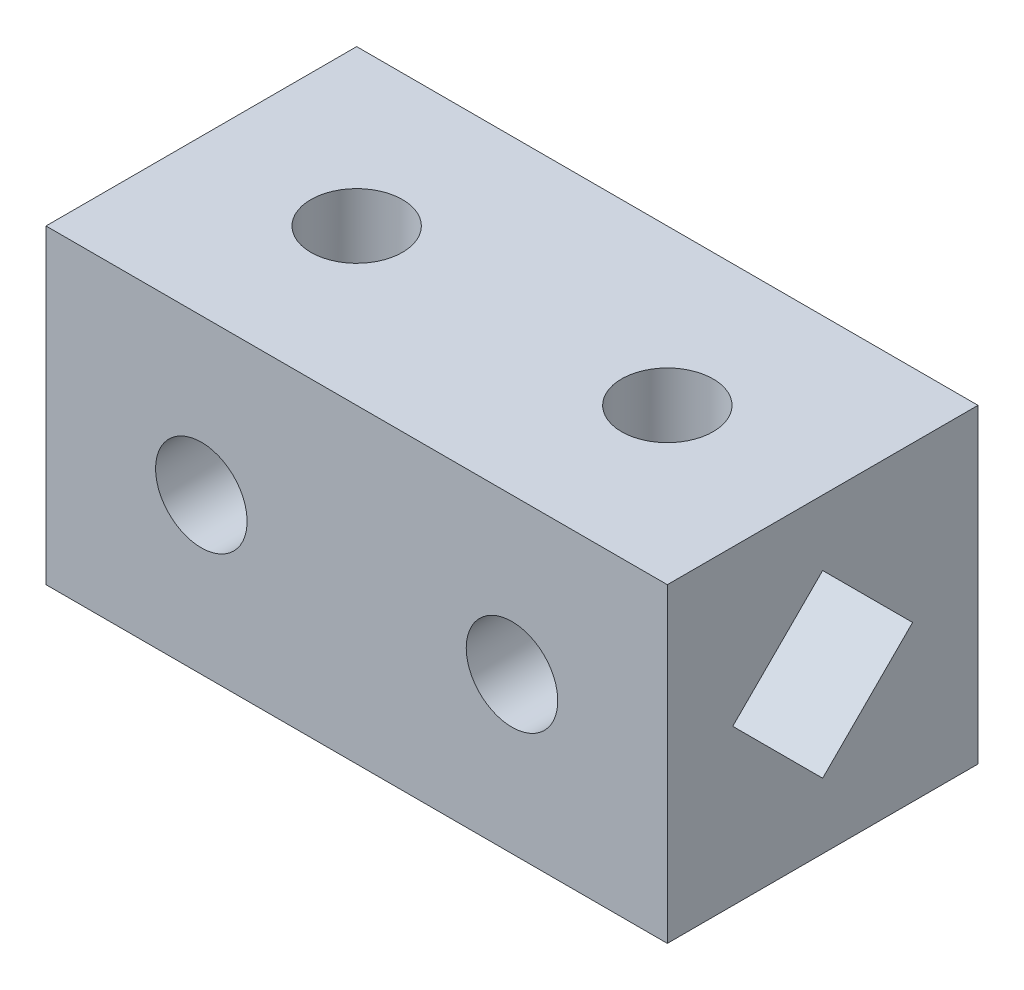
SolidWorks part; units mm, degrees
ref_plane "Front Plane" through (0, 0, 0) normal (0, 0, 1) x (1, 0, 0)
ref_plane "Top Plane" through (0, 0, 0) normal (0, 1, 0) x (1, 0, 0)
ref_plane "Right Plane" through (0, 0, 0) normal (1, 0, 0) x (0, 0, -1)
other "Configuration Table"
sketch "sketch1" plane through (0, 0, 0) normal (0, 1, 0) x (1, 0, 0)
  line L0 (0, -8.5) -> (8.5, -8.5) construction
  line L1 (0, 0) -> (34, 0)
  line L2 (0, 0) -> (0, -17)
  line L3 (0, -17) -> (34, -17)
  line L4 (34, 0) -> (34, -17)
  line L5 (8.5, -8.5) -> (25.5, -8.5) construction
  circle A1 centre (8.5, -8.5) radius 2.505
  circle A2 centre (25.5, -8.5) radius 2.505
  dimension "D4" = 5.01
  dimension "D1" = 17
  dimension "D2" = 34
  dimension "D3" = 8.5
  dimension "D6" = 17
extrude "Boss-Extrude1" add sketch "sketch1" along normal blind 17
sketch "Sketch6" plane through (0, 0, 0) normal (0, 0, -1) x (-1, 0, 0)
  line L0 (-34, 8.5) -> (-25.5, 8.5) construction
  line L1 (-25.5, 8.5) -> (-8.5, 8.5) construction
  line L4 (-34, 0) -> (0, 0)
  line L5 (0, 0) -> (0, 17)
  line L6 (0, 17) -> (-34, 17)
  line L7 (-34, 17) -> (-34, 0)
  line L8 (-34, 0) -> (0, 0)
  line L9 (0, 0) -> (0, 17)
  line L10 (0, 17) -> (-34, 17)
  line L11 (-34, 17) -> (-34, 0)
  circle A0 centre (-25.5, 8.5) radius 2.505
  circle A1 centre (-8.5, 8.5) radius 2.505
  dimension "D3" = 5.01
  dimension "D2" = 8.5
  dimension "D5" = 17
  dimension "D4" = 2
extrude "Cut-Extrude10" cut sketch "Sketch6" against normal through all flip side to cut
sketch "Sketch7" plane through (34, 0, 0) normal (1, 0, 0) x (0, 0, -1)
  line L0 (-17, 8.5) -> (0, 8.5) construction
  line L1 (-8.5, 8.5) -> (-8.5, 13.4215) construction
  line L2 (-8.5, 13.4215) -> (-3.5785, 8.5)
  line L3 (-3.5785, 8.5) -> (-8.5, 3.5785)
  line L4 (-17, 0) -> (0, 0)
  line L5 (0, 0) -> (0, 17)
  line L6 (0, 17) -> (-17, 17)
  line L7 (-17, 17) -> (-17, 0)
  line L8 (-17, 0) -> (0, 0)
  line L9 (0, 0) -> (0, 17)
  line L10 (0, 17) -> (-17, 17)
  line L11 (-17, 17) -> (-17, 0)
  line L12 (-8.5, 3.5785) -> (-13.4215, 8.5)
  line L13 (-13.4215, 8.5) -> (-8.5, 13.4215)
  dimension "D2" = 6.96
extrude "Cut-Extrude11" cut sketch "Sketch7" against normal blind 34 flip side to cut
equation "\"D2@sketch1\" = \"length\""
equation "\"holes\" = 2"
equation "\"cdist\"= 17mm'centre distance between holes"
equation "\"width\"= 17mm"
equation "\"length\"= \"cdist\" * \"holes\""
equation "\"D1@sketch1\" = \"width\""
equation "\"hdiam\"= 5.01mm'Hole diametre"
equation "\"D4@sketch1\" = \"hdiam\""
equation "\"D6@sketch1\" = \"cdist\""
equation "\"D5@sketch1\" = \"holes\""
equation "\"D2@Sketch6\"=\"cdist\"/2"
equation "\"D3@Sketch6\"=\"hdiam\""
equation "\"D5@Sketch6\"=\"cdist\""
equation "\"D4@Sketch6\"=\"holes\""
equation "\"D1@Boss-Extrude1\"=\"width\""
equation "\"insetwidth\"= 7mm"
equation "\"tolerance\"= 0.04mm"
equation "\"D2@Sketch7\"=\"insetwidth\"-\"tolerance\""
equation "\"D1@Cut-Extrude11\"=\"length\""
